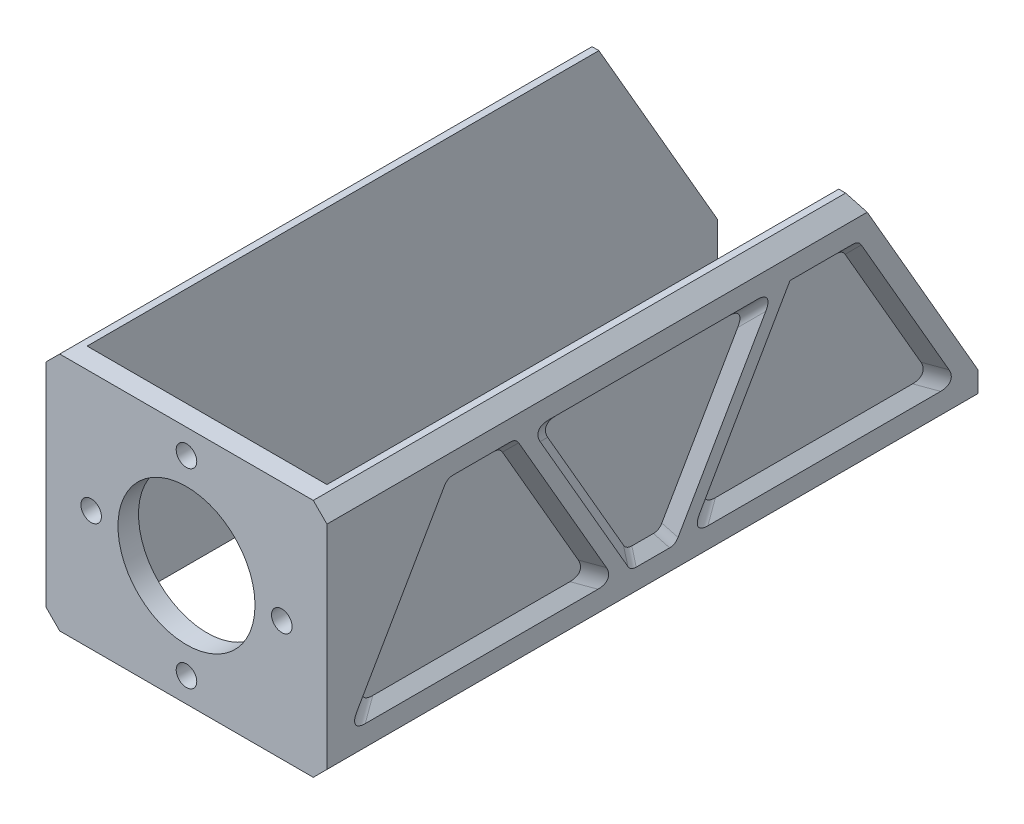
SolidWorks part; units mm, degrees
material "Alumina"
ref_plane "Front Plane" through (0, 0, 0) normal (0, 0, 1) x (1, 0, 0)
ref_plane "Top Plane" through (0, 0, 0) normal (0, 1, 0) x (1, 0, 0)
ref_plane "Right Plane" through (0, 0, 0) normal (1, 0, 0) x (0, 0, -1)
sketch "Sketch1" plane through (0, 0, 0) normal (0, 0, 1) x (1, 0, 0)
  line L1 (0, 0) -> (35, 0)
  line L2 (0, 0) -> (0, 35)
  line L3 (0, 35) -> (35, 35)
  line L4 (35, 0) -> (35, 35)
  dimension "D1" = 35
  dimension "D2" = 35
extrude "Boss-Extrude1" add sketch "Sketch1" along normal blind 3
sketch "Sketch2" plane through (0, 0, 3) normal (0, 0, 1) x (1, 0, 0)
  circle A0 centre (17.5, 17.5) radius 10
  dimension "D1" = 20
extrude "Cut-Extrude1" cut sketch "Sketch2" against normal through all
sketch "Sketch4" plane through (0, 0, 0) normal (-1, 0, 0) x (0, 0, 1)
  line L1 (3, 35) -> (-92, 35)
  line L2 (3, 35) -> (3, 0)
  line L3 (3, 0) -> (-92, 0)
  line L4 (-92, 35) -> (-92, 0)
  dimension "D1" = 95
extrude "Boss-Extrude2" add sketch "Sketch4" along normal blind 3
sketch "Sketch6" plane through (35, 0, 0) normal (1, 0, 0) x (0, 0, -1)
  line L1 (-3, 35) -> (92, 35)
  line L2 (-3, 35) -> (-3, 0)
  line L3 (-3, 0) -> (92, 0)
  line L4 (92, 35) -> (92, 0)
extrude "Boss-Extrude5" add sketch "Sketch6" along normal blind 3
chamfer "Chamfer1" distance 2 angle 45 4 edges at (-3, 0, -44.5) (38, 0, -44.5) (38, 35, -44.5) (-3, 35, -44.5)
sketch "Sketch7" plane through (-3, 0, 0) normal (-1, 0, 0) x (0, 0, 1)
  line L3 (-89, 5) -> (-50.1325, 5)
  line L5 (-92, 2) -> (3, 2) construction
  line L8 (-89, 5) -> (-74.5662, 30)
  line L9 (-74.5662, 30) -> (-64.5662, 30)
  line L10 (-64.5662, 30) -> (-50.1325, 5)
  line L11 (-39, 5) -> (-24.5662, 30)
  line L12 (-24.5662, 30) -> (-14.5662, 30)
  line L13 (-14.5662, 30) -> (-0.1325, 5)
  line L14 (-39, 5) -> (-0.1325, 5)
  dimension "D1" = 2
  dimension "D2" = 3
  dimension "D6" = 60
  dimension "D7" = 10
extrude "Cut-Extrude3" cut sketch "Sketch7" against normal blind 1.5
sketch "Sketch8" plane through (-3, 0, 0) normal (-1, 0, 0) x (0, 0, 1)
  line L0 (-47.8231, 5) -> (-41.3094, 5)
  line L1 (-41.3094, 5) -> (-26.8756, 30)
  line L2 (-26.8756, 30) -> (-62.2568, 30)
  line L3 (-62.2568, 30) -> (-47.8231, 5)
  line L4 (-50.1325, 5) -> (-64.5662, 30) construction
  line L5 (-24.5662, 30) -> (-39, 5) construction
  line L6 (-89, 5) -> (-50.1325, 5) construction
  line L7 (-64.5662, 30) -> (-74.5662, 30) construction
  line L8 (-24.5662, 30) -> (-39, 5) construction
  dimension "D1" = 2
  dimension "D2" = 2
extrude "Cut-Extrude4" cut sketch "Sketch8" against normal blind 1.5
sketch "Sketch9" plane through (38, 0, 0) normal (1, 0, 0) x (0, 0, -1)
  line L0 (0.1325, 5) -> (14.5662, 30)
  line L1 (14.5662, 30) -> (24.5662, 30)
  line L2 (24.5662, 30) -> (39, 5)
  line L3 (39, 5) -> (0.1325, 5)
  line L4 (41.3094, 5) -> (47.8231, 5)
  line L5 (47.8231, 5) -> (62.2568, 30)
  line L6 (62.2568, 30) -> (26.8756, 30)
  line L7 (26.8756, 30) -> (41.3094, 5)
  line L8 (50.1325, 5) -> (89, 5)
  line L9 (89, 5) -> (74.5662, 30)
  line L10 (74.5662, 30) -> (64.5662, 30)
  line L11 (64.5662, 30) -> (50.1325, 5)
extrude "Cut-Extrude5" cut sketch "Sketch9" against normal blind 1.5
chamfer "Chamfer3" distance 1.5 angle 45 24 edges at (-1.5, 17.5, -31.7831) (-1.5, 30, -19.5662) (-1.5, 17.5, -7.3494) (-1.5, 5, -19.5662) (-1.5, 30, -44.5662) (-1.5, 17.5, -34.0925) (-1.5, 5, -44.5662) (-1.5, 17.5, -55.04) (-1.5, 30, -69.5662) (-1.5, 17.5, -57.3494) (-1.5, 5, -69.5662) (-1.5, 17.5, -81.7831) (36.5, 30, -69.5662) (36.5, 17.5, -81.7831) (36.5, 5, -69.5662) (36.5, 17.5, -57.3494) (36.5, 30, -44.5662) (36.5, 17.5, -55.04) (36.5, 5, -44.5662) (36.5, 17.5, -34.0925) (36.5, 17.5, -7.3494) (36.5, 30, -19.5662) (36.5, 17.5, -31.7831) (36.5, 5, -19.5662)
sketch "Sketch10" plane through (-3, 0, 0) normal (-1, 0, 0) x (0, 0, 1)
  line L0 (-92, 5) -> (-74.6795, 35)
  line L1 (-92, 33) -> (-92, 2) construction
  line L2 (-92, 35) -> (3, 35) construction
  line L3 (-74.6795, 35) -> (-92, 35)
  line L4 (-92, 35) -> (-92, 5)
  line L7 (-74.5662, 30) -> (-89, 5) construction
  point P6 (0, 0)
  dimension "D1" = 30
extrude "Cut-Extrude6" cut sketch "Sketch10" against normal through all
sketch "Sketch11" plane through (0, 0, 3) normal (0, 0, 1) x (1, 0, 0)
  circle A0 centre (17.5, 17.5) radius 13.91
  circle A1 centre (17.5, 31.41) radius 1.5
  circle A2 centre (31.41, 17.5) radius 1.5
  circle A3 centre (17.5, 17.5) radius 13.91
  circle A4 centre (17.5, 3.59) radius 1.5
  circle A5 centre (17.5, 17.5) radius 13.91
  circle A6 centre (3.59, 17.5) radius 1.5
  circle A7 centre (17.5, 17.5) radius 13.91
  point P17 (17.5, 17.5)
  dimension "D1" = 27.82
  dimension "D2" = 3
  dimension "D3" = 4
extrude "Cut-Extrude7" cut sketch "Sketch11" against normal through all contours A6 | A1 | A2 | A4
fillet "Fillet3" radius 2 23 edges at (37.25, 5.75, -1.4315) (37.25, 29.25, -14.9993) (37.25, 29.25, -24.1332) (37.25, 5.75, -37.701) (37.25, 29.25, -74.1332) (37.25, 5.75, -87.701) (37.25, 29.25, -28.1747) (37.25, 29.25, -60.9578) (37.25, 5.75, -41.7424) (37.25, 5.75, -47.3901) (37.25, 5.75, -51.4315) (-2.25, 5.75, -1.4315) (-2.25, 5.75, -37.701) (-2.25, 29.25, -14.9993) (-2.25, 29.25, -24.1332) (-2.25, 29.25, -28.1747) (-2.25, 5.75, -41.7424) (-2.25, 5.75, -47.3901) (-2.25, 5.75, -51.4315) (-2.25, 29.25, -64.9993) (-2.25, 29.25, -60.9578) (-2.25, 29.25, -74.1332) (-2.25, 5.75, -87.701)
